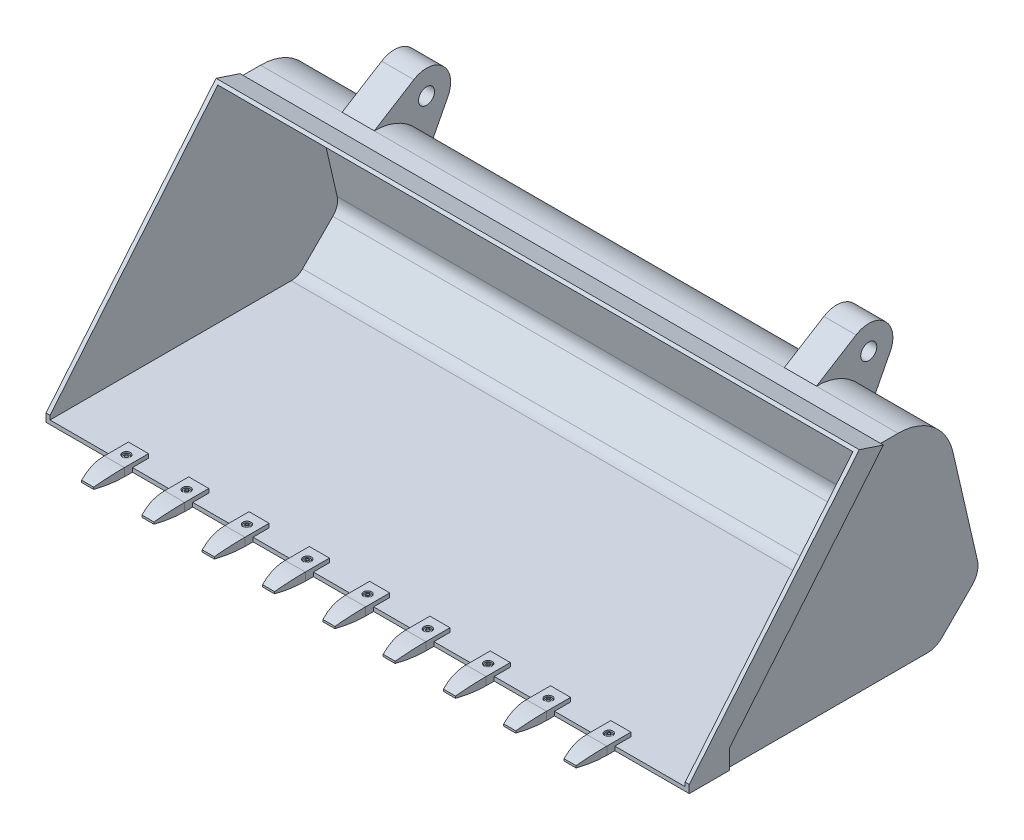
SolidWorks part; units mm, degrees
ref_plane "Płaszczyzna przednia" through (0, 0, 0) normal (0, 0, 1) x (1, 0, 0)
ref_plane "Płaszczyzna górna" through (0, 0, 0) normal (0, 1, 0) x (1, 0, 0)
ref_plane "Płaszczyzna prawa" through (0, 0, 0) normal (1, 0, 0) x (0, 0, -1)
sketch "Szkic2" plane through (0, 0, 0) normal (1, 0, 0) x (0, 0, -1)
  line L0 (-300, 0) -> (300, 0)
  line L1 (-300, 0) -> (-300, 20)
  line L5 (335.3553, 14.6447) -> (410.7144, 90.0038)
  line L6 (424.0776, 136.6067) -> (363.0157, 401.0947)
  line L7 (226.6039, 509.6016) -> (182.965, 509.6016)
  line L8 (182.965, 509.6016) -> (122.965, 529.6016)
  line L9 (122.965, 529.6016) -> (-300, 20)
  arc A0 (410.7144, 90.0038) -> (424.0776, 136.6067) centre (375.3591, 125.3591) ccw
  arc A1 (300, 0) -> (335.3553, 14.6447) centre (300, 50) ccw
  arc A2 (226.6039, 509.6016) -> (363.0157, 401.0947) centre (226.6039, 369.6016) cw
  point P12 (430.3122, 109.6016)
  point P15 (320.7107, 0)
  point P18 (337.965, 509.6016)
  dimension "D9" = 50
  dimension "D11" = 140
  dimension "D1" = 20
  dimension "D2" = 135
  dimension "D3" = 122
  dimension "D4" = 155
  dimension "D5" = 400
  dimension "D6" = 155
  dimension "D7" = 20
  dimension "D8" = 60
  dimension "D10" = 600
extrude "Dodanie-wyciągnięcie1" add sketch "Szkic2" along normal mid plane 1600
sketch "Szkic3" plane through (0, 0, 0) normal (1, 0, 0) x (0, 0, -1)
  line L7 (126.2915, 517.9518) -> (117.4513, 522.9586)
  line L8 (122.965, 529.6016) -> (-300, 20) construction
  line L9 (117.4513, 522.9586) -> (-308.2999, 10)
  line L10 (-308.2999, 10) -> (-290, 10)
  line L14 (-290, 16.3907) -> (-290, 10)
  line L15 (-290, 10) -> (300, 10)
  line L16 (328.2843, 21.7157) -> (403.6434, 97.0748)
  line L17 (414.3339, 134.3571) -> (353.272, 398.8452)
  line L18 (226.6039, 499.6016) -> (181.3422, 499.6016)
  line L19 (181.3422, 499.6016) -> (126.2915, 517.9518)
  line L20 (126.2915, 517.9518) -> (-290, 16.3907)
  line L22 (-290, 10) -> (300, 10)
  line L23 (328.2843, 21.7157) -> (403.6434, 97.0748)
  line L24 (414.3339, 134.3571) -> (353.272, 398.8452)
  line L25 (226.6039, 499.6016) -> (181.3422, 499.6016)
  line L26 (181.3422, 499.6016) -> (126.2915, 517.9518)
  arc A6 (300, 10) -> (328.2843, 21.7157) centre (300, 50) ccw
  arc A7 (403.6434, 97.0748) -> (414.3339, 134.3571) centre (375.3591, 125.3591) ccw
  arc A8 (353.272, 398.8452) -> (226.6039, 499.6016) centre (226.6039, 369.6016) ccw
  arc A9 (300, 10) -> (328.2843, 21.7157) centre (300, 50) ccw
  arc A10 (403.6434, 97.0748) -> (414.3339, 134.3571) centre (375.3591, 125.3591) ccw
  arc A11 (353.272, 398.8452) -> (226.6039, 499.6016) centre (226.6039, 369.6016) ccw
  dimension "D1" = 10
extrude "Wytnij-wyciągnięcie1" cut sketch "Szkic3" against normal mid plane 1580
sketch "Szkic4" plane through (800, 0, 0) normal (1, 0, 0) x (0, 0, -1)
  line L0 (226.6039, 509.6016) -> (182.965, 509.6016) construction
  line L1 (424.0776, 136.6067) -> (363.0157, 401.0947) construction
  line L2 (335.3553, 14.6447) -> (410.7144, 90.0038) construction
  line L3 (-300, 0) -> (300, 0) construction
  line L4 (226.6039, 509.6016) -> (182.965, 509.6016)
  line L5 (424.0776, 136.6067) -> (363.0157, 401.0947)
  line L6 (335.3553, 14.6447) -> (410.7144, 90.0038)
  line L7 (-200, 0) -> (300, 0)
  line L8 (182.965, 509.6016) -> (-200, 48.1933)
  line L9 (-200, 48.1933) -> (-200, 0)
  line L10 (122.965, 529.6016) -> (-300, 20) construction
  arc A0 (363.0157, 401.0947) -> (226.6039, 509.6016) centre (226.6039, 369.6016) ccw construction
  arc A1 (410.7144, 90.0038) -> (424.0776, 136.6067) centre (375.3591, 125.3591) ccw construction
  arc A2 (300, 0) -> (335.3553, 14.6447) centre (300, 50) ccw construction
  arc A3 (363.0157, 401.0947) -> (226.6039, 509.6016) centre (226.6039, 369.6016) ccw
  arc A4 (410.7144, 90.0038) -> (424.0776, 136.6067) centre (375.3591, 125.3591) ccw
  arc A5 (300, 0) -> (335.3553, 14.6447) centre (300, 50) ccw
  dimension "D1" = 500
extrude "Wytnij-wyciągnięcie2" cut sketch "Szkic4" against normal blind 7
ref_plane "Płaszczyzna1" through (590, 0, 0) normal (1, 0, 0) x (0, 0, -1)
sketch "Szkic5" plane through (590, 0, 0) normal (1, 0, 0) x (0, 0, -1)
  line L0 (226.6039, 509.6016) -> (324.9889, 570.5966)
  line L1 (409.9346, 492.109) -> (363.0157, 401.0947)
  arc A0 (363.0157, 401.0947) -> (226.6039, 509.6016) centre (226.6039, 369.6016) ccw construction
  arc A1 (363.0157, 401.0947) -> (226.6039, 509.6016) centre (226.6039, 369.6016) ccw
  circle A2 centre (356.6039, 519.6016) radius 20
  arc A3 (324.9889, 570.5966) -> (409.9346, 492.109) centre (356.6039, 519.6016) cw
  dimension "D3" = 40
  dimension "D4" = 60
  dimension "D1" = 150
  dimension "D2" = 130
extrude "Dodanie-wyciągnięcie2" add sketch "Szkic5" against normal blind 80
mirror "Lustro1" about plane through (0, 0, 0) normal (1, 0, 0) of "Dodanie-wyciągnięcie2", "Wytnij-wyciągnięcie2"
sketch "Szkic6" plane through (590, 0, 0) normal (1, 0, 0) x (0, 0, -1)
  line L0 (-260, 10) -> (-260, 20)
  line L1 (-300, 10) -> (300, 10) construction
  line L2 (-260, 10) -> (-300, 10)
  line L3 (-300, 20) -> (-300, 0) construction
  line L4 (-300, 10) -> (-300, 0)
  line L5 (-300, 0) -> (-385.3835, 0)
  line L6 (-385.3835, 0) -> (-385.3835, 5)
  line L7 (-260, 20) -> (-320, 20)
  arc A0 (-320, 20) -> (-385.3835, 5) centre (-320, -130) ccw
  dimension "D5" = 150
  dimension "D1" = 10
  dimension "D2" = 10
  dimension "D3" = 60
  dimension "D4" = 5
  dimension "D6" = 40
extrude "Dodanie-wyciągnięcie3" add sketch "Szkic6" along normal mid plane 50 separate body
sketch "Szkic8" plane through (0, 20, 0) normal (0, 1, 0) x (1, 0, 0)
  line L0 (615, -260) -> (565, -320) construction
  line L1 (615, -320) -> (565, -320) construction
  circle A0 centre (590, -290) radius 6
  dimension "D1" = 12
extrude "Wytnij-wyciągnięcie3" cut sketch "Szkic8" against normal through all
sketch "Szkic9" plane through (0, 20, 0) normal (0, 1, 0) x (1, 0, 0)
  circle A0 centre (589.9775, -290.0411) radius 10
  dimension "D1" = 20
extrude "Wytnij-wyciągnięcie4" cut sketch "Szkic9" against normal blind 10
sketch "Szkic10" plane through (0, 10, 0) normal (0, 1, 0) x (1, 0, 0)
  circle A0 centre (590, -290) radius 8.5
  dimension "D1" = 17
extrude "Dodanie-wyciągnięcie4" add sketch "Szkic10" along normal blind 8
fillet "Zaokrąglenie1" radius 1 1 edges at (590, 18, 298.5)
sketch "Szkic11" plane through (0, 10, 0) normal (0, 1, 0) x (1, 0, 0)
  circle A1 centre (590, -290) radius 6
  dimension "D1" = 12
extrude "Dodanie-wyciągnięcie5" add sketch "Szkic11" against normal blind 8
sketch "Szkic13" plane through (0, 18, 0) normal (0, 1, 0) x (1, 0, 0)
  line L1 (595.2527, -291.6306) -> (594.0385, -286.2663)
  line L2 (594.0385, -286.2663) -> (588.7857, -284.6357)
  line L3 (588.7857, -284.6357) -> (584.7473, -288.3694)
  line L4 (584.7473, -288.3694) -> (585.9615, -293.7337)
  line L5 (585.9615, -293.7337) -> (591.2143, -295.3643)
  line L6 (591.2143, -295.3643) -> (595.2527, -291.6306)
  circle A0 centre (590, -290) radius 4.7631 construction
  dimension "D1" = 5.5
extrude "Wytnij-wyciągnięcie5" cut sketch "Szkic13" against normal blind 4
sketch "Szkic14" plane through (0, 0, 0) normal (0, -1, 0) x (1, 0, 0)
  line L0 (590, 385.3835) -> (590, 333.0902) construction
  line L1 (615, 385.3835) -> (565, 385.3835) construction
  line L2 (615, 320) -> (631.1618, 320)
  line L3 (565, 320) -> (546.078, 320)
  line L4 (546.078, 320) -> (546.078, 396.5544)
  line L5 (546.078, 396.5544) -> (631.1618, 396.5544)
  line L6 (631.1618, 396.5544) -> (631.1618, 320)
  arc A0 (615, 320) -> (603.9629, 385.3835) centre (415.8166, 320) ccw
  arc A1 (565, 320) -> (573.9629, 385.3835) centre (807.9648, 320) cw
  point P14 (603.9629, 385.3835)
  point P18 (0, 0)
  dimension "D1" = 30
extrude "Wytnij-wyciągnięcie6" cut sketch "Szkic14" against normal through all and the other way through all
pattern_linear "Szyk liniowy3" count 9 spacing 150 along (-1, 0, 0) of "Dodanie-wyciągnięcie3", "Wytnij-wyciągnięcie3", "Wytnij-wyciągnięcie4", "Dodanie-wyciągnięcie4", "Zaokrąglenie1", "Dodanie-wyciągnięcie5", "Wytnij-wyciągnięcie5", "Wytnij-wyciągnięcie6"
